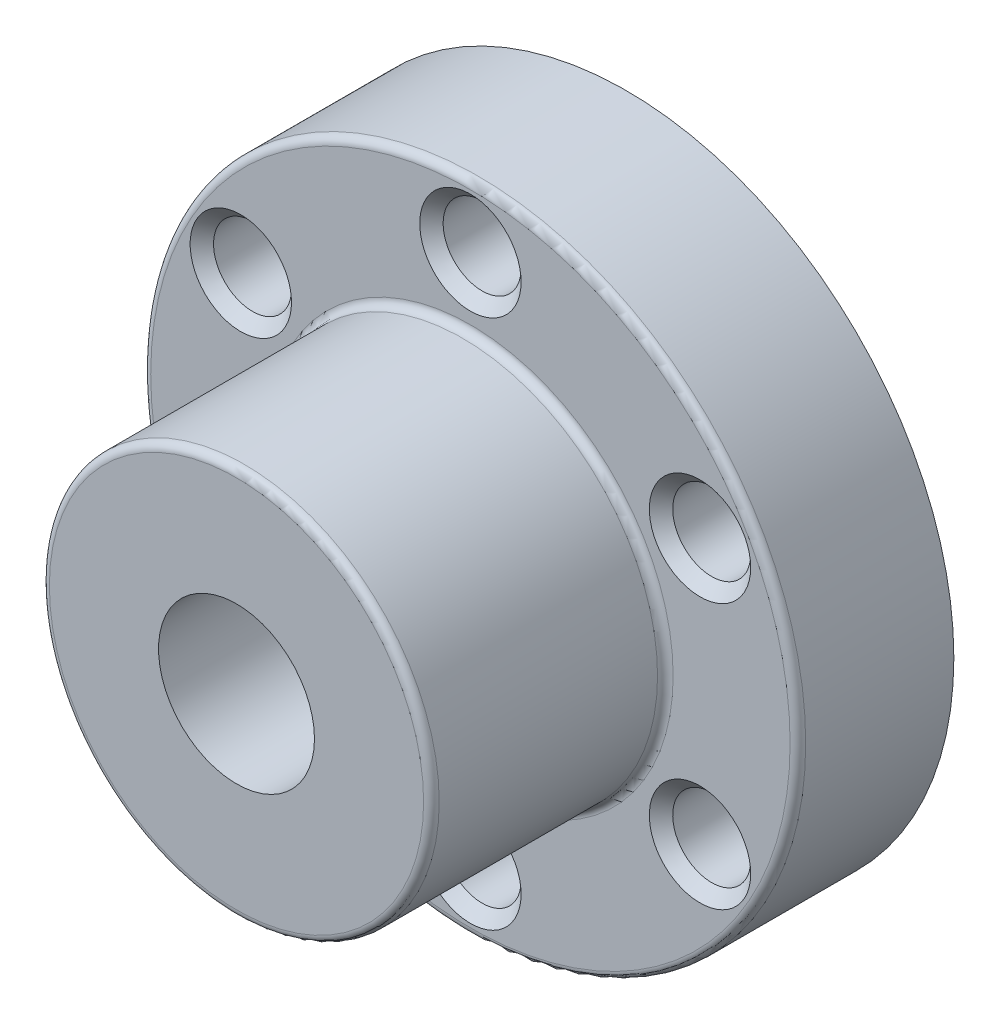
SolidWorks part; units mm, degrees
material "ABS"
ref_plane "Front Plane" through (0, 0, 0) normal (0, 0, 1) x (1, 0, 0)
ref_plane "Top Plane" through (0, 0, 0) normal (0, 1, 0) x (1, 0, 0)
ref_plane "Right Plane" through (0, 0, 0) normal (1, 0, 0) x (0, 0, -1)
sketch "Sketch1" plane through (0, 0, 0) normal (0, 0, 1) x (1, 0, 0)
  circle A0 centre (0, 0) radius 21
  dimension "D1" = 42
extrude "Boss-Extrude1" add sketch "Sketch1" along normal blind 10
sketch "Sketch2" plane through (0, 0, 10) normal (0, 0, 1) x (1, 0, 0)
  circle A0 centre (0, 0) radius 12.5
  dimension "D1" = 25
extrude "Boss-Extrude2" add sketch "Sketch2" along normal blind 15
sketch "Sketch3" plane through (0, 0, 25) normal (0, 0, 1) x (1, 0, 0)
  circle A0 centre (0, 0) radius 5
  dimension "D1" = 10
extrude "Cut-Extrude1" cut sketch "Sketch3" against normal through all
sketch "Sketch4" plane through (0, 0, 0) normal (0, 0, -1) x (-1, 0, 0)
  circle A0 centre (0, 0) radius 17 construction
  circle A1 centre (0, 17) radius 2.5
  dimension "D1" = 34
  dimension "D2" = 5
extrude "Cut-Extrude2" cut sketch "Sketch4" against normal through all
fillet "Fillet1" radius 0.5 3 edges at (21, 0, 10) (12.5, 0, 10) (12.5, 0, 25)
chamfer "Chamfer2" distance 0.75 angle 45 1 edges at (2.5, 17, 10)
pattern_circular "CirPattern2" count 6 over 360 about axis through (0, 0, 10) along (0, 0, -1) of "Chamfer2", "Cut-Extrude2"
